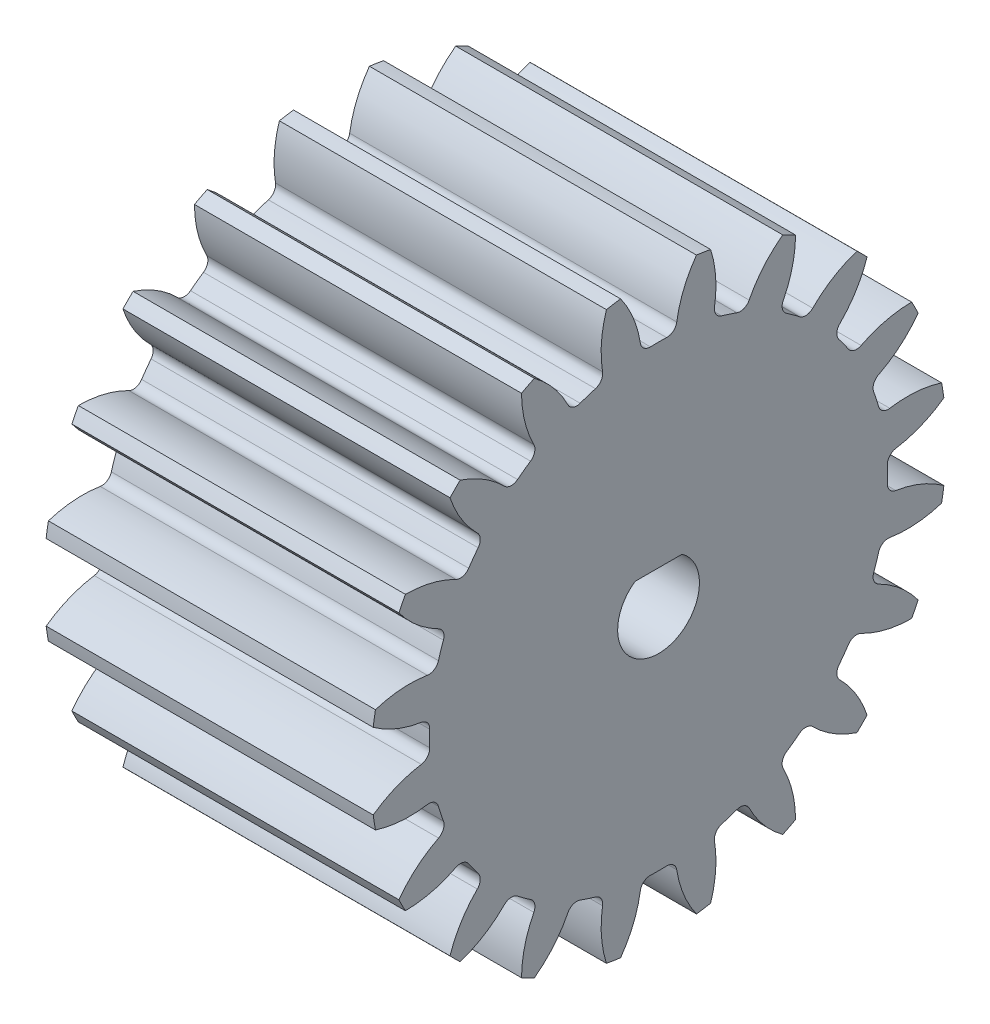
SolidWorks part; units mm, degrees
ref_plane "Front Plane" through (0, 0, 0) normal (0, 0, 1) x (1, 0, 0)
ref_plane "Top Plane" through (0, 0, 0) normal (0, 1, 0) x (1, 0, 0)
ref_plane "Right Plane" through (0, 0, 0) normal (1, 0, 0) x (0, 0, -1)
sketch "Sketch1" plane through (0, 0, 0) normal (1, 0, 0) x (0, 0, -1)
  circle A0 centre (0, 0) radius 3.125
  circle A1 centre (0, 0) radius 22
  dimension "D1" = 6.25
  dimension "D2" = 44
extrude "Boss-Extrude2" add sketch "Sketch1" along normal blind 25
sketch "Sketch3" plane through (25, 0, 0) normal (1, 0, 0) x (0, 0, -1)
  line L0 (0, 0) -> (0, 22) construction
  line L1 (-1.3128, 17.4507) -> (0, 0) construction
  line L2 (0, 14.7782) -> (-1.4216, 18.684) construction
  circle A0 centre (0, 0) radius 22 construction
  arc A1 (1.3128, 17.4507) -> (-1.3128, 17.4507) centre (0, 0) ccw
  arc A2 (1.8708, 19.9123) -> (-1.8708, 19.9123) centre (0, 0) ccw construction
  arc A3 (2.8988, 21.8082) -> (-2.8988, 21.8082) centre (0, 0) ccw
  arc A4 (-2.8988, 21.8082) -> (-1.3128, 17.4507) centre (-9.8582, 16.8078) cw
  arc A5 (2.8988, 21.8082) -> (1.3128, 17.4507) centre (9.8582, 16.8078) ccw
  point P17 (-1.8055, 19.7388)
  dimension "D1" = 44
  dimension "D2" = 40
  dimension "D3" = 4.5
  dimension "D4" = 20
  dimension "D5" = 3.7416
extrude "Cut-Extrude1" cut sketch "Sketch3" against normal through all
fillet "Fillet1" radius 0.76 2 edges at (12.5, 17.4507, -1.3128) (12.5, 17.4507, 1.3128)
pattern_circular "CirPattern2" count 20 over 360 about axis through (25, 0, 0) along (1, 0, 0) of "Fillet1", "Cut-Extrude1"
sketch "Sketch4" plane through (0, 0, 0) normal (-1, 0, 0) x (0, 0, 1)
  line L0 (1.2919, -2.8455) -> (3, -2.8455) construction
  line L5 (-1.8, 2.5545) -> (1.8, 2.5545)
  circle A0 centre (0, 0) radius 3.125 construction
  arc A1 (-1.8, 2.5545) -> (1.8, 2.5545) centre (0, 0.1545) cw
  dimension "D2" = 3
  dimension "D1" = 5.4
  dimension "D3" = 3.6
extrude "Boss-Extrude3" add sketch "Sketch4" against normal up to surface (25 mm away) up to face at (25, 0, -3.125)
equation "\"No of teeth\" = 20"
equation "\"Module\"= 2"
equation "\"Outer Diameter\"= ( \"No of teeth\" + 2 ) * \"Module\""
equation "\"Pitch Diameter\"= \"No of teeth\" * \"Module\""
equation "\"Backlash\"= 0.3 * \"Module\""
equation "\"Arc Length\"= ( ( \"Module\" * pi ) / 2 ) + \"Backlash\""
equation "\"Fillet Radius\"= 0.38 * \"Module\""
equation "\"Bore Diameter\"= 6.25"
equation "\"Presseure angle\"= 20"
equation "\"Tooth Design\"= IIF ( \"Module\" <= 1.25 , 2.4 * \"Module\" , 2.25 * \"Module\" )"
equation "\"D1@Sketch1\"=\"Bore Diameter\""
equation "\"D2@Sketch1\"=\"Outer Diameter\""
equation "\"D1@Sketch3\"=\"Outer Diameter\""
equation "\"D2@Sketch3\"=\"Pitch Diameter\""
equation "\"D3@Sketch3\"=\"Tooth Design\""
equation "\"D4@Sketch3\"=\"Presseure angle\""
equation "\"D5@Sketch3\"=\"Arc Length\""
equation "\"D1@Fillet1\"=\"Fillet Radius\""
equation "\"D1@CirPattern2\"=\"No of teeth\""
